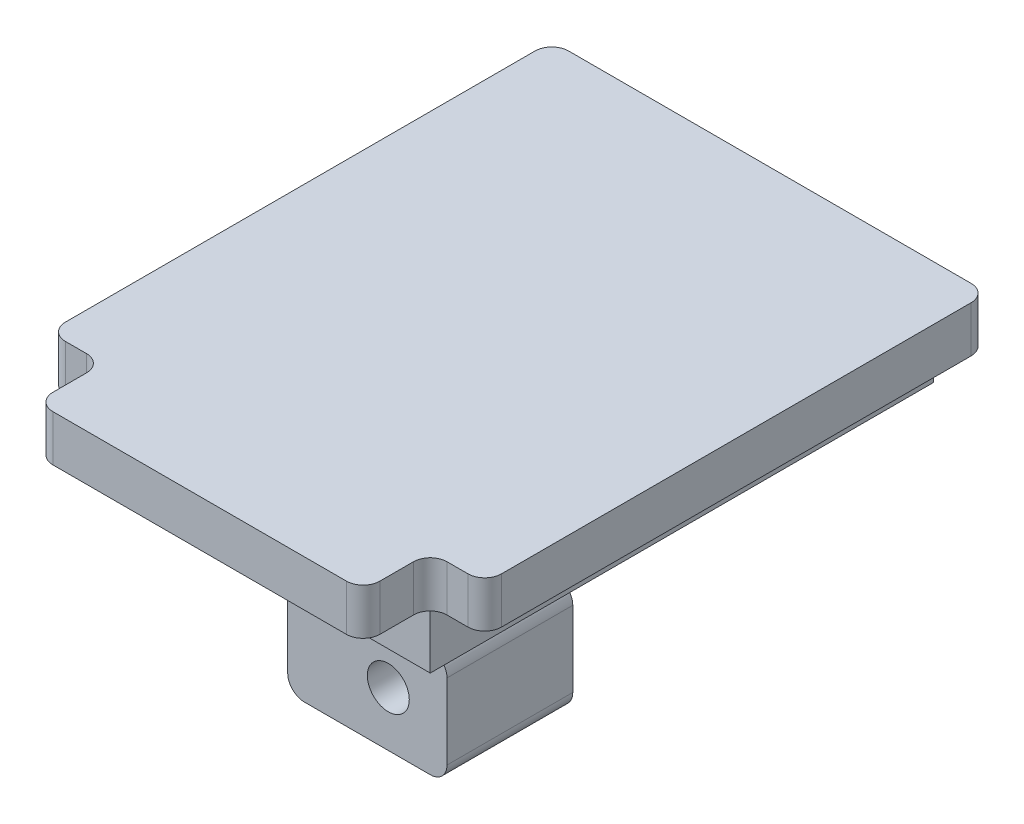
SolidWorks part; units mm, degrees
ref_plane "Front Plane" through (0, 0, 0) normal (0, 0, 1) x (1, 0, 0)
ref_plane "Top Plane" through (0, 0, 0) normal (0, 1, 0) x (1, 0, 0)
ref_plane "Right Plane" through (0, 0, 0) normal (1, 0, 0) x (0, 0, -1)
sketch "Sketch1" plane through (0, 0, 0) normal (0, 0, 1) x (1, 0, 0)
  line L1 (-26, 0) -> (26, 0)
  line L2 (26, 0) -> (26, -5.5)
  line L3 (26, -5.5) -> (19.5, -5.5)
  line L4 (19.5, -5.5) -> (19.5, -12.5)
  line L5 (19.5, -12.5) -> (-19.5, -12.5)
  line L6 (-19.5, -12.5) -> (-19.5, -5.5)
  line L7 (-19.5, -5.5) -> (-26, -5.5)
  line L8 (-26, -5.5) -> (-26, 0)
  point P7 (0, 0)
  dimension "D1" = 7
  dimension "D2" = 52
  dimension "D3" = 5.5
  dimension "D4" = 39
extrude "Boss-Extrude1" add sketch "Sketch1" along normal blind 60
sketch "Sketch2" plane through (0, 0, 60) normal (0, 0, 1) x (1, 0, 0)
  line L0 (-26, -5.5) -> (-19.5, -5.5) construction
  line L1 (-19.5, -5.5) -> (19.5, -5.5)
  line L2 (-19.5, -5.5) -> (-19.5, 0)
  line L3 (-19.5, 0) -> (19.5, 0)
  line L4 (19.5, -5.5) -> (19.5, 0)
  line L5 (-19.5, -5.5) -> (-19.5, -12.5) construction
  line L6 (19.5, -12.5) -> (19.5, -5.5) construction
  line L7 (26, 0) -> (-26, 0) construction
extrude "Boss-Extrude2" add sketch "Sketch2" along normal blind 8
fillet "Fillet2" radius 2 8 edges at (-19.5, -2.75, 60) (-26, -2.75, 0) (26, -2.75, 0) (-26, -2.75, 60) (26, -2.75, 60) (19.5, -2.75, 60) (-19.5, -2.75, 68) (19.5, -2.75, 68)
sketch "Sketch3" plane through (0, -12.5, 0) normal (0, -1, 0) x (1, 0, 0)
  line L0 (-19.5, 0) -> (19.5, 0) construction
  line L1 (-3, 45.5) -> (3, 45.5)
  line L2 (-3, 45.5) -> (-3, 30.5)
  line L3 (-3, 30.5) -> (3, 30.5)
  line L4 (3, 45.5) -> (3, 30.5)
  line L5 (-3, 45.5) -> (3, 30.5) construction
  line L6 (-3, 30.5) -> (3, 45.5) construction
  point P0 (0, 38)
  dimension "D1" = 15
  dimension "D2" = 6
  dimension "D3" = 38
extrude "Boss-Extrude3" add sketch "Sketch3" along normal blind 12
sketch "Sketch4" plane through (0, -24.5, 0) normal (0, -1, 0) x (1, 0, 0)
  line L0 (-3, 45.5) -> (-3, 30.5) construction
  line L1 (-12, 45.5) -> (7, 45.5)
  line L2 (-12, 45.5) -> (-12, 30.5)
  line L3 (-12, 30.5) -> (7, 30.5)
  line L4 (7, 45.5) -> (7, 30.5)
  line L7 (3, 45.5) -> (-3, 45.5) construction
  line L10 (-3, 30.5) -> (3, 30.5) construction
  dimension "D1" = 9
  dimension "D2" = 19
extrude "Boss-Extrude4" add sketch "Sketch4" along normal blind 13
fillet "Fillet3" radius 2 6 edges at (3, -24.5, 38) (7, -24.5, 38) (7, -37.5, 38) (-12, -37.5, 38) (-12, -24.5, 38) (-3, -24.5, 38)
sketch "Sketch5" plane through (0, 0, 45.5) normal (0, 0, 1) x (1, 0, 0)
  line L0 (7, -35.5) -> (7, -26.5) construction
  circle A0 centre (0, -31) radius 2.5
  point P4 (0, 0)
  point P7 (7, -31)
  dimension "D1" = 5
extrude "Cut-Extrude1" cut sketch "Sketch5" against normal through all
